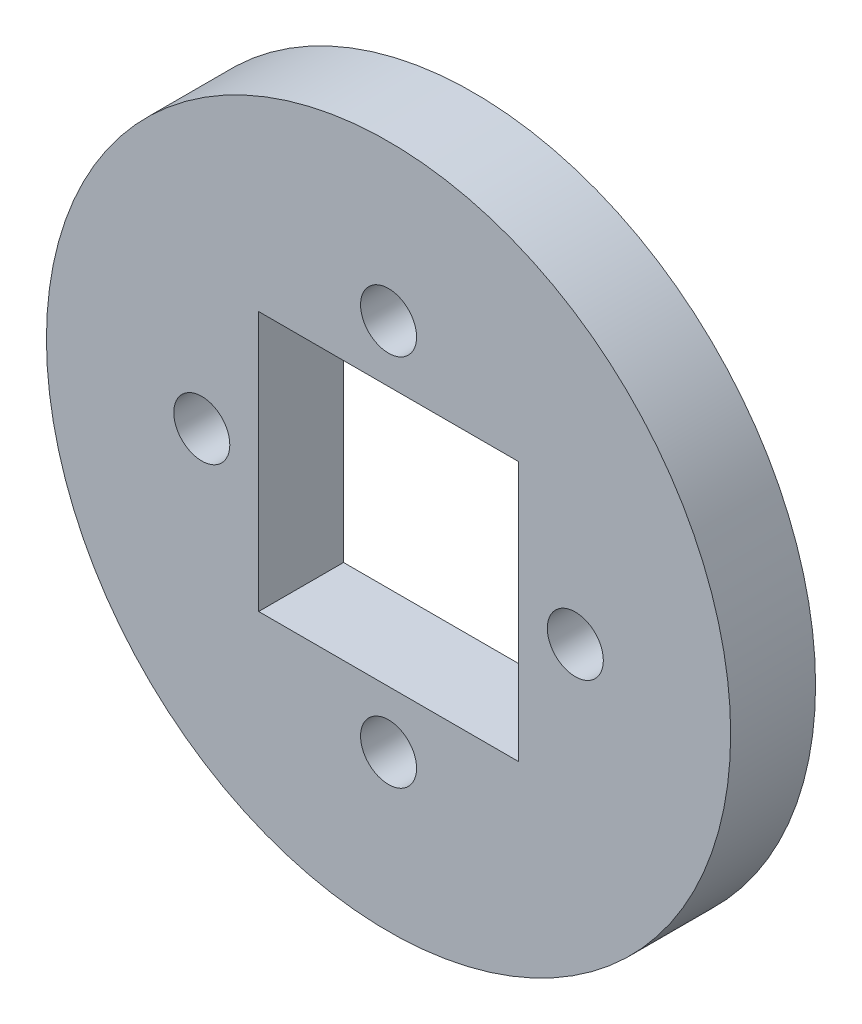
SolidWorks part; units mm, degrees
ref_plane "Front Plane" through (0, 0, 0) normal (0, 0, 1) x (1, 0, 0)
ref_plane "Top Plane" through (0, 0, 0) normal (0, 1, 0) x (1, 0, 0)
ref_plane "Right Plane" through (0, 0, 0) normal (1, 0, 0) x (0, 0, -1)
sketch "Sketch1" plane through (0, 0, 0) normal (0, 0, 1) x (1, 0, 0)
  line L0 (-15.3, 15.3) -> (-15.3, -15.3) construction
  line L1 (-15.3, -15.3) -> (15.3, -15.3) construction
  line L2 (15.3, -15.3) -> (15.3, 15.3) construction
  line L3 (15.3, 15.3) -> (-15.3, 15.3) construction
  line L4 (-15.3, 15.3) -> (-15.3, -15.3)
  line L5 (-15.3, -15.3) -> (15.3, -15.3)
  line L6 (15.3, -15.3) -> (15.3, 15.3)
  line L7 (15.3, 15.3) -> (-15.3, 15.3)
  arc A0 (-29.1461, 27.8315) -> (30.772, 26.0226) centre (0, 0) ccw construction
  arc A1 (-29.1461, 27.8315) -> (30.772, 26.0226) centre (0, 0) ccw construction
  circle A2 centre (0, 0) radius 40.3
  circle A3 centre (0, 22) radius 1.65
  circle A4 centre (22, 0) radius 1.65
  circle A5 centre (0, -22) radius 1.65
  circle A6 centre (-22, 0) radius 1.65
  dimension "D1" = 3.3
extrude "Boss-Extrude1" add sketch "Sketch1" along normal blind 10
sketch "Sketch2" plane through (0, 0, 10) normal (0, 0, 1) x (1, 0, 0)
  circle A0 centre (22, 0) radius 3.3
  circle A1 centre (0, 22) radius 3.3
  circle A2 centre (-22, 0) radius 3.3
  circle A3 centre (0, -22) radius 3.3
  dimension "D1" = 6.6
extrude "Cut-Extrude1" cut sketch "Sketch2" against normal blind 6
